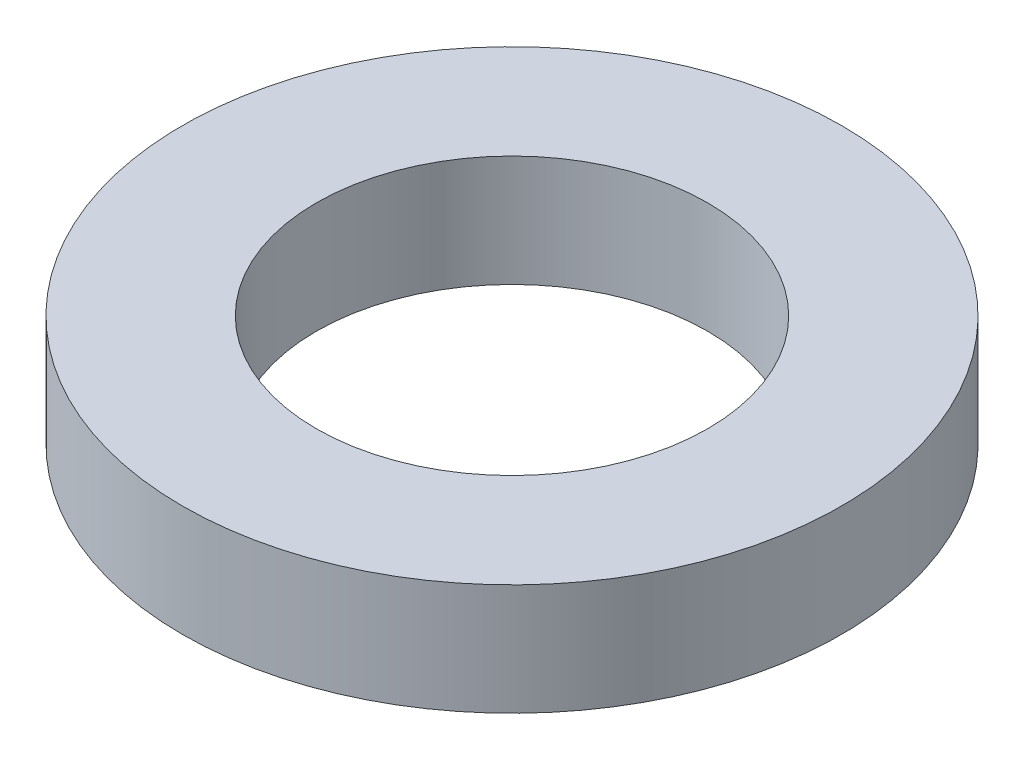
SolidWorks part; units mm, degrees
ref_plane "Front Plane" through (0, 0, 0) normal (0, 0, 1) x (1, 0, 0)
ref_plane "Top Plane" through (0, 0, 0) normal (0, 1, 0) x (1, 0, 0)
ref_plane "Right Plane" through (0, 0, 0) normal (1, 0, 0) x (0, 0, -1)
sketch "Sketch1" plane through (0, 0, 0) normal (0, 1, 0) x (1, 0, 0)
  circle A0 centre (0, 0) radius 80
  dimension "FLANGE_OD" = 160
extrude "Boss-Extrude1" add sketch "Sketch1" along normal blind 27
sketch "Sketch2" plane through (0, 0, 0) normal (0, 1, 0) x (1, 0, 0)
  circle A0 centre (0, 0) radius 47.5
  dimension "BORE_D" = 95
extrude "Cut-Extrude1" cut sketch "Sketch2" along normal through all
sketch "Sketch3" plane through (0, 27, 0) normal (0, 1, 0) x (1, 0, 0)
  circle A0 centre (0, 0) radius 27.9338 construction
  circle A1 centre (-27.9338, 0) radius 2.1703
  dimension "BOLT_D" = 4.3406
  dimension "BOLT_PCD" = 55.8676
extrude "Cut-Extrude2" cut sketch "Sketch3" against normal blind 26.0365 rebuild error yes
pattern_circular "CirPattern1" count 4 over 360 rebuild error yes
